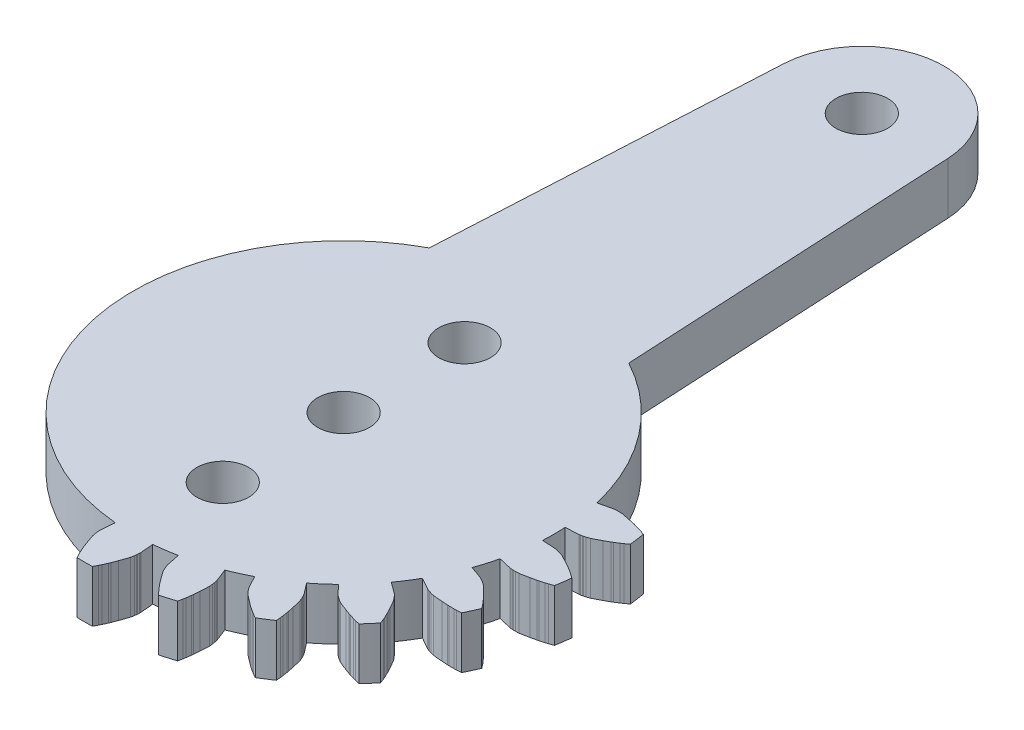
SolidWorks part; units mm, degrees
material "普通碳钢"
ref_plane "前视" through (0, 0, 0) normal (0, 0, 1) x (1, 0, 0)
ref_plane "上视" through (0, 0, 0) normal (0, 1, 0) x (1, 0, 0)
ref_plane "右视" through (0, 0, 0) normal (1, 0, 0) x (0, 0, -1)
sketch "草图1" plane through (0, 0, 0) normal (0, 1, 0) x (1, 0, 0)
  line L0 (39.751, 40.5224) -> (39.6866, 41.2679)
  line L1 (39.6866, 41.2679) -> (39.6851, 41.3287)
  line L2 (39.6851, 41.3287) -> (39.6859, 41.3577)
  line L3 (39.6859, 41.3577) -> (39.6916, 41.4528)
  line L4 (39.6916, 41.4528) -> (39.6929, 41.4698)
  line L5 (39.6929, 41.4698) -> (39.6966, 41.5042)
  line L6 (39.6966, 41.5042) -> (39.712, 41.6258)
  line L7 (39.712, 41.6258) -> (39.7121, 41.6267)
  line L8 (39.7121, 41.6267) -> (39.7482, 41.8247)
  line L9 (39.9295, 42.3366) -> (40.044, 42.6442)
  line L10 (40.044, 42.6442) -> (40.0454, 42.6478)
  line L11 (40.0454, 42.6478) -> (40.0855, 42.7398)
  line L12 (40.0855, 42.7398) -> (40.1995, 42.9971)
  line L13 (41.9203, 40.5224) -> (41.9848, 41.2679)
  line L14 (41.9848, 41.2679) -> (41.9862, 41.3287)
  line L15 (41.9862, 41.3287) -> (41.9855, 41.3577)
  line L16 (41.9855, 41.3577) -> (41.9797, 41.4528)
  line L17 (41.9797, 41.4528) -> (41.9784, 41.4698)
  line L18 (41.9784, 41.4698) -> (41.9748, 41.5042)
  line L19 (41.9748, 41.5042) -> (41.9594, 41.6258)
  line L20 (41.9594, 41.6258) -> (41.9592, 41.6267)
  line L21 (41.9592, 41.6267) -> (41.9231, 41.8247)
  line L22 (41.7419, 42.3366) -> (41.6274, 42.6442)
  line L23 (41.6274, 42.6442) -> (41.626, 42.6478)
  line L24 (41.626, 42.6478) -> (41.5858, 42.7398)
  line L25 (41.5858, 42.7398) -> (41.4718, 42.9971)
  circle A0 centre (40.8357, 28.3833) radius 12.1875 construction
  arc A1 (39.751, 40.5224) -> (41.9203, 40.5224) centre (40.8357, 28.3833) cw
  arc A2 (41.9231, 41.8247) -> (41.7419, 42.3366) centre (25.8953, 36.4382) ccw
  arc A4 (39.9295, 42.3366) -> (39.7482, 41.8247) centre (55.7761, 36.4382) ccw
  arc A5 (40.2653, 43.1347) -> (40.1995, 42.9971) centre (42.6892, 41.8899) ccw
  arc A6 (40.3945, 43.3768) -> (40.2653, 43.1347) centre (48.1168, 39.1026) ccw
  arc A11 (41.4718, 42.9971) -> (41.406, 43.1347) centre (38.9822, 41.8899) ccw
  arc A12 (41.406, 43.1347) -> (41.2769, 43.3768) centre (33.5546, 39.1026) ccw
  arc A13 (41.2769, 43.3768) -> (40.3945, 43.3768) centre (40.8357, 28.3833) ccw
  dimension "D1" = 24.375
extrude "凸台-拉伸1" add sketch "草图1" along normal blind 3 contours A4 L8 L7 L6 L5 L4 L3 L2 L1 L0 A1 L13 L14 L15 L16 L17 L18 L19 L20 L21 A2 L22 L23 L24 L25 A11 A12 A13 A6 A5 L12 L11 L10 L9
sketch "草图2" plane through (0, 0, 0) normal (0, -1, 0) x (1, 0, 0)
  circle A0 centre (40.8357, -28.3833) radius 12.1875
  circle A1 centre (40.8357, -28.3833) radius 1.5
  circle A2 centre (40.8357, -28.3833) radius 7 construction
  circle A3 centre (40.8357, -21.3833) radius 1.5
  circle A4 centre (40.8357, -35.3833) radius 1.5
  dimension "D1" = 3
  dimension "D2" = 24.375
  dimension "D3" = 14
  dimension "D4" = 3
  dimension "D5" = 3
extrude "凸台-拉伸2" add sketch "草图2" against normal blind 3
pattern_circular "阵列(圆周)2" count 22 over 360 about axis through (40.8357, 3, -28.3833) along (0, -1, 0) of "凸台-拉伸1"
sketch "草图3" plane through (0, 0, 0) normal (0, -1, 0) x (-1, 0, 0)
  circle A0 centre (-40.8357, 28.3833) radius 13.75
  dimension "D1" = 27.5
sketch "草图5" plane through (0, 0, 0) normal (0, -1, 0) x (1, 0, 0)
  line L0 (40.8357, -19.8833) -> (40.8357, -63.1398) construction
  line L1 (45.5857, -58.6327) -> (46.6107, -39.1157)
  line L2 (36.0857, -58.6327) -> (35.0607, -39.1157)
  circle A0 centre (40.8357, -21.3833) radius 1.5 construction
  circle A2 centre (40.8357, -28.3833) radius 12.1875 construction
  arc A3 (53.0056, -29.0373) -> (53.0056, -27.7293) centre (40.8357, -28.3833) ccw construction
  arc A4 (36.0857, -58.6327) -> (45.5857, -58.6327) centre (40.8357, -58.3833) ccw
  circle A5 centre (40.8357, -58.3833) radius 1.5
  arc A6 (35.0607, -39.1157) -> (46.6107, -39.1157) centre (40.8357, -28.3833) ccw
  dimension "D4" = 3
  dimension "D1" = 11.55
  dimension "D2" = 9.5
  dimension "D3" = 30
extrude "凸台-拉伸3" add sketch "草图5" against normal blind 3
sketch "草图7" plane through (0, 0, 0) normal (0, -1, 0) x (1, 0, 0)
  line L0 (36.0857, -58.6327) -> (34.9723, -37.4337) construction
  line L1 (35.0751, -39.3907) -> (36.0857, -58.6327) construction
  line L2 (45.5857, -58.6327) -> (46.7591, -36.2892) construction
  line L3 (45.5857, -58.6327) -> (46.5962, -39.3907) construction
  line L4 (35.0607, -39.1157) -> (35.0751, -39.3907)
  line L5 (35.0751, -39.3907) -> (34.8365, -39.8437)
  line L6 (34.8365, -39.8437) -> (33.6211, -45.0698)
  line L7 (33.6211, -45.0698) -> (23.2947, -35.4215)
  line L8 (23.2947, -35.4215) -> (25.1891, -22.1682)
  line L9 (25.1891, -22.1682) -> (31.4308, -11.204)
  line L10 (31.4308, -11.204) -> (37.9696, -9.817)
  line L11 (37.9696, -9.817) -> (39.751, -16.2441)
  line L12 (46.6107, -39.1157) -> (46.5962, -39.3907)
  line L13 (46.5962, -39.3907) -> (47.0142, -42.3632)
  line L14 (52.3284, -32.4394) -> (55.4375, -32.4394)
  line L15 (55.4375, -32.4394) -> (53.5277, -41.7128)
  line L16 (53.5277, -41.7128) -> (47.0142, -42.3632)
  arc A0 (35.0607, -39.1157) -> (39.751, -16.2441) centre (40.8357, -28.3833) cw
  circle A1 centre (40.8357, -28.3833) radius 1.5 construction
  circle A2 centre (40.8357, -28.3833) radius 12.1875 construction
  arc A3 (46.6107, -39.1157) -> (52.3284, -32.4394) centre (40.8357, -28.3833) ccw
extrude "切除-拉伸1" cut sketch "草图7" against normal blind 3
sketch "草图8" plane through (0, 0, 0) normal (0, -1, 0) x (-1, 0, 0)
  line L0 (-40.8357, 35.3833) -> (-40.8357, 21.3833)
